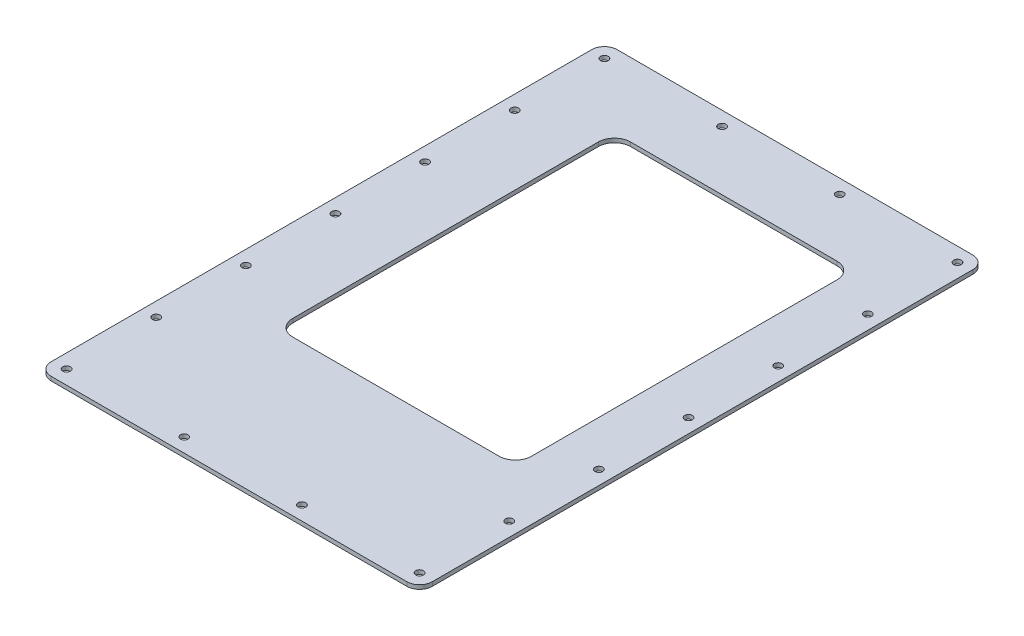
SolidWorks part; units mm, degrees
material "5052-H32"
ref_plane "Front Plane" through (0, 0, 0) normal (0, 0, 1) x (1, 0, 0)
ref_plane "Top Plane" through (0, 0, 0) normal (0, 1, 0) x (1, 0, 0)
ref_plane "Right Plane" through (0, 0, 0) normal (1, 0, 0) x (0, 0, -1)
sketch "Sketch9" plane through (0, 0, 0) normal (0, 1, 0) x (1, 0, 0)
  line L0 (-149.5, 0) -> (-149.5, 444)
  line L13 (-149.5, 444) -> (149.5, 444)
  line L14 (103.1625, 121.4438) -> (-84.1625, 121.4438)
  line L19 (149.5, 444) -> (149.5, 0)
  line L20 (103.1625, 121.4438) -> (103.1625, 386.5563)
  line L21 (103.1625, 386.5563) -> (-84.1625, 386.5563)
  line L22 (-84.1625, 121.4438) -> (-84.1625, 386.5563)
  line L23 (103.1625, 254) -> (-84.1625, 254) construction
  line L24 (9.5, 386.5562) -> (9.5, 121.4438) construction
  line L25 (-149.5, 0) -> (149.5, 0)
  point P8 (0, 0)
  point P19 (0, 0)
  dimension "D3" = 265.1125
  dimension "D4" = 187.325
  dimension "D1" = 299
  dimension "D2" = 444
  dimension "D6" = 140
  dimension "D5" = 190
extrude "Boss-Extrude7" add sketch "Sketch9" along normal blind 3.175 separate body contours L0 L25 L19 L13 L14 L22 L21 L20 region at (-144.1471, 0, -222)
fillet "Fillet4" radius 10 4 edges at (-149.5, 1.5875, -444) (149.5, 1.5875, -444) (-149.5, 1.5875, 0) (149.5, 1.5875, 0)
fillet "Fillet5" radius 12.7 4 edges at (-84.1625, 1.5875, -121.4438) (103.1625, 1.5875, -121.4438) (103.1625, 1.5875, -386.5563) (-84.1625, 1.5875, -386.5563)
sketch "Sketch10" plane through (0, 3.175, 0) normal (0, 1, 0) x (1, 0, 0)
  line L0 (-149.5, 10) -> (-149.5, 434) construction
  line L1 (-139.5, 0) -> (139.5, 0) construction
  circle A0 centre (-138.5, 11) radius 3
  circle A1 centre (-46.1667, 11) radius 3
  circle A2 centre (46.1667, 11) radius 3
  circle A3 centre (138.5, 11) radius 3
  circle A56 centre (-138.5, 81.3333) radius 3
  circle A57 centre (-138.5, 151.6667) radius 3
  circle A58 centre (-138.5, 222) radius 3
  circle A59 centre (-138.5, 292.3333) radius 3
  circle A60 centre (-138.5, 362.6667) radius 3
  circle A61 centre (-138.5, 433) radius 3
  circle A68 centre (138.5, 81.3333) radius 3
  circle A72 centre (138.5, 151.6667) radius 3
  circle A76 centre (138.5, 222) radius 3
  circle A80 centre (138.5, 292.3333) radius 3
  circle A84 centre (138.5, 362.6667) radius 3
  circle A86 centre (-46.1667, 433) radius 3
  circle A87 centre (46.1667, 433) radius 3
  circle A88 centre (138.5, 433) radius 3
  circle A102 centre (-46.1667, 81.3333) radius 3 [skipped]
  circle A103 centre (46.1667, 81.3333) radius 3 [skipped]
  circle A104 centre (-46.1667, 151.6667) radius 3 [skipped]
  circle A105 centre (46.1667, 151.6667) radius 3 [skipped]
  circle A106 centre (-46.1667, 222) radius 3 [skipped]
  circle A107 centre (46.1667, 222) radius 3 [skipped]
  circle A108 centre (-46.1667, 292.3333) radius 3 [skipped]
  circle A109 centre (46.1667, 292.3333) radius 3 [skipped]
  circle A110 centre (-46.1667, 362.6667) radius 3 [skipped]
  circle A111 centre (46.1667, 362.6667) radius 3 [skipped]
  dimension "D1" = 6
  dimension "D2" = 11
  dimension "D3" = 11
  dimension "D6" = 70.3333
  dimension "D7" = 92.3333
  dimension "D4" = 4
extrude "Cut-Extrude1" cut sketch "Sketch10" against normal up to surface (3.175 mm away) up to face at (9.5, 0, -254)
equation "\"W\"= 255"
equation "\"L\"= 400"
equation "\"Offset\"= 30"
equation "\"H\"= 110"
equation "\"Compartment Width\"= 80"
equation "\"T\"= 4.7625 * 2 / 3"
equation "\"Inside Fillet Radius\"= 5.55625"
equation "\"Hole\"=15"
equation "\"Wheel to Wall\"= 50"
equation "\"D1@Sketch9\"=\"W\"+44"
equation "\"D2@Sketch9\"=\"L\"+44"
equation "\"D6@Sketch10\"=(\"L\"+22)/6"
equation "\"D7@Sketch10\"=(\"W\"+22)/3"
equation "\"D5@Sketch9\"=(\"L\"/2+20)-\"Offset\""
